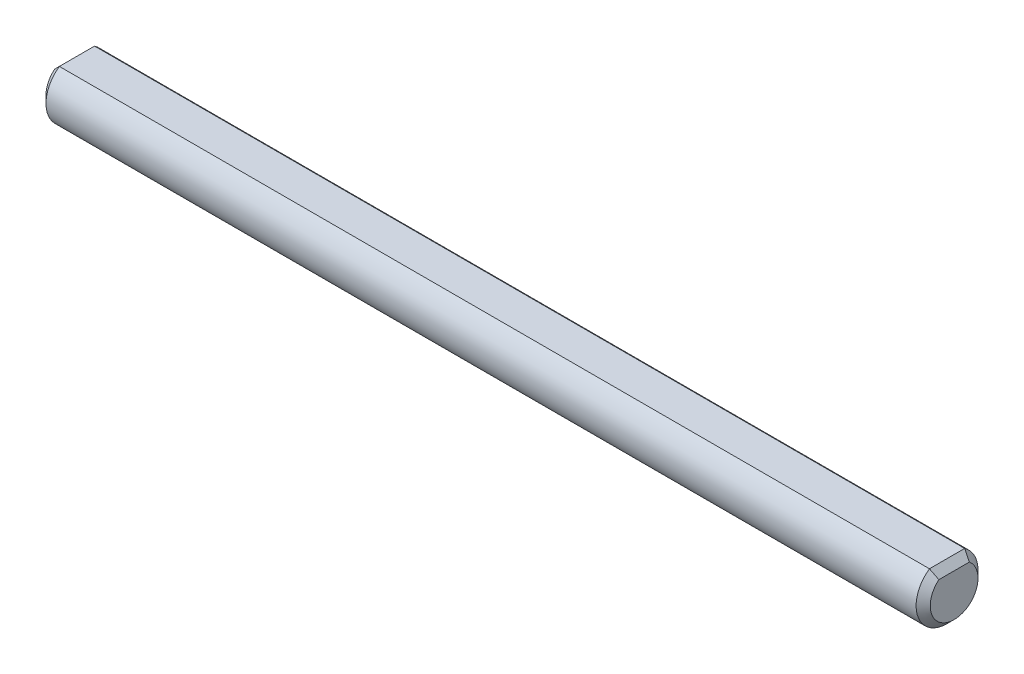
SolidWorks part; units mm, degrees
ref_plane "Front Plane" through (0, 0, 0) normal (0, 0, 1) x (1, 0, 0)
ref_plane "Top Plane" through (0, 0, 0) normal (0, 1, 0) x (1, 0, 0)
ref_plane "Right Plane" through (0, 0, 0) normal (1, 0, 0) x (0, 0, -1)
sketch "Sketch1" plane through (0, 0, 0) normal (1, 0, 0) x (0, 0, -1)
  line L1 (0.9955, 1.4392) -> (-0.9955, 1.4392)
  arc A0 (-0.9955, 1.4392) -> (0.9955, 1.4392) centre (0, 0) ccw
  dimension "D1" = 3.5
extrude "Boss-Extrude1" add sketch "Sketch1" along normal mid plane 50
chamfer "Chamfer1" distance 0.4 angle 45 4 edges at (-25, 1.4392, 0) (-25, -1.75, 0) (25, 1.4392, 0) (25, -1.75, 0)
